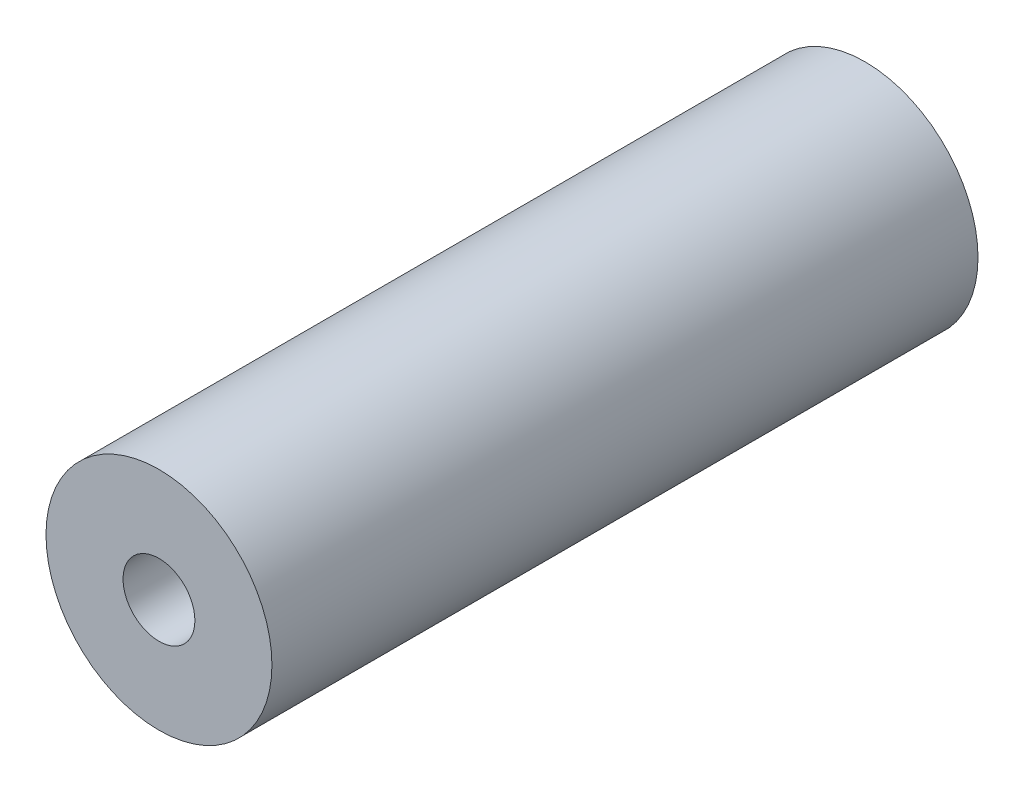
SolidWorks part; units mm, degrees
material "6061-T6 (SS)"
ref_plane "Front Plane" through (0, 0, 0) normal (0, 0, 1) x (1, 0, 0)
ref_plane "Top Plane" through (0, 0, 0) normal (0, 1, 0) x (1, 0, 0)
ref_plane "Right Plane" through (0, 0, 0) normal (1, 0, 0) x (0, 0, -1)
sketch "Sketch1" plane through (0, 0, 0) normal (0, 0, 1) x (1, 0, 0)
  circle A1 centre (0, 0) radius 6.35
  dimension "D2" = 12.7
extrude "Boss-Extrude1" add sketch "Sketch1" along normal mid plane 39.6875 contours A1 region at (0, 0, 0)
hole_wizard "#10-32 Tapped Hole1" positions "3DSketch1" profile "Sketch2" tap size "#10-32" standard "ANSI Inch"
sketch3d "3DSketch1"
  line L0 (0, 0, 19.8438) -> (0, 0, -19.8438) construction
  point P0 (0, 0, 19.8438)
  point P4 (0, 0, -19.8438)
sketch "Sketch2" plane through (0, 0, 19.8438) normal (1, 0, 0) x (0, -1, 0)
  line L0 (0, 0) -> (0, 13.2428)
  line L1 (0, 13.2428) -> (2.0193, 12.0294)
  line L2 (2.0193, 12.0294) -> (2.0193, 0)
  line L5 (2.0193, 0) -> (0, 0)
  line L10 (0, 13.2428) -> (-2.0193, 12.0294) construction
  line L11 (0, -6.35) -> (0, 107.95) construction
  dimension "Tap Drill Dia." = 4.0386
  dimension "Tap Drill Depth" = 12.0294
  dimension "Drill Angle" = 118
cosmetic thread "Hole Thread1"
cosmetic thread "Hole Thread2"
